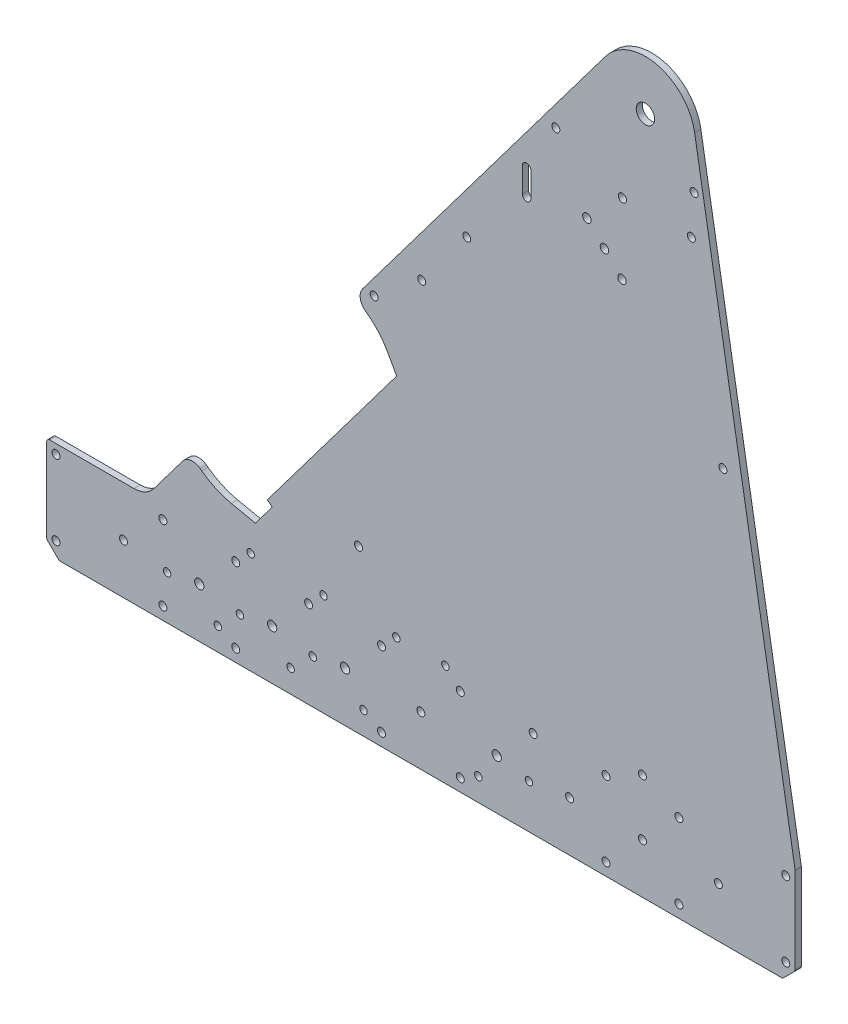
SolidWorks part; units mm, degrees
ref_plane "Front Plane" through (0, 0, 0) normal (0, 0, 1) x (1, 0, 0)
ref_plane "Top Plane" through (0, 0, 0) normal (0, 1, 0) x (1, 0, 0)
ref_plane "Right Plane" through (0, 0, 0) normal (1, 0, 0) x (0, 0, -1)
sketch "Sketch1" plane through (0, 0, 0) normal (0, 0, 1) x (1, 0, 0)
  line L1 (0, 0) -> (381, 0)
  line L2 (0, 0) -> (0, 50.8)
  line L4 (381, 0) -> (381, 50.8)
  line L5 (381, 50.8) -> (329.8374, 350.3513)
  line L6 (0, 50.8) -> (44.463, 50.8)
  line L7 (54.6105, 55.8634) -> (73.025, 80.3327)
  line L9 (112.3265, 79.755) -> (178.1676, 167.245)
  line L11 (157.0275, 191.9556) -> (284.5049, 361.3482)
  line L12 (112.3265, 79.755) -> (114.8634, 77.8458)
  line L13 (114.8634, 77.8458) -> (106.2722, 66.4299)
  line L14 (157.0275, 191.9556) -> (169.7119, 182.4098)
  line L15 (169.7119, 182.4098) -> (178.1676, 167.245)
  line L16 (73.025, 80.3327) -> (85.7094, 70.7869)
  line L17 (85.7094, 70.7869) -> (106.2722, 66.4299)
  line L18 (169.7119, 182.4098) -> (85.7094, 70.7869) construction
  arc A0 (284.5049, 361.3482) -> (329.8374, 350.3513) centre (304.8, 346.075) cw
  arc A1 (44.463, 50.8) -> (54.6105, 55.8634) centre (44.463, 63.5) ccw
  point P11 (50.8, 50.8)
  dimension "D4" = 346.075
  dimension "D7" = 12.7
  dimension "D5" = 25.4
  dimension "D1" = 50.8
  dimension "D2" = 381
  dimension "D3" = 76.2
  dimension "D6" = 50.8
  dimension "D8" = 123.825
  dimension "D9" = 139.7
  dimension "D10" = 15.875
  dimension "D11" = 31.75
  dimension "D12" = 73.025
  dimension "D13" = 3.175
  dimension "D14" = 14.2875
  dimension "D15" = 115
extrude "Boss-Extrude1" add sketch "Sketch1" along normal blind 3.175
sketch "Sketch2" plane through (0, 0, 3.175) normal (0, 0, 1) x (1, 0, 0)
  line L1 (190.5, 50.8) -> (190.5, 0) construction
  line L3 (0, 0) -> (381, 0) construction
  line L5 (0, 6.35) -> (0, 0)
  line L6 (0, 50.8) -> (0, 0) construction
  line L7 (0, 0) -> (6.35, 0)
  line L8 (6.35, 0) -> (0, 6.35)
  line L9 (381, 0) -> (374.65, 0)
  line L10 (374.65, 0) -> (381, 6.35)
  line L11 (381, 6.35) -> (381, 0)
  circle A19 centre (4.7625, 46.0375) radius 2.032
  circle A20 centre (4.7625, 7.9375) radius 2.032
  circle A21 centre (376.2375, 7.9375) radius 2.032
  circle A22 centre (376.2375, 46.0375) radius 2.032
  dimension "D21" = 6.35
  dimension "D27" = 4.064
  dimension "D4" = 46.0375
  dimension "D22" = 6.35
  dimension "D25" = 4.7625
  dimension "D28" = 7.9375
extrude "Cut-Extrude1" cut sketch "Sketch2" against normal up to next
sketch "Sketch5" plane through (0, 0, 3.175) normal (0, 0, 1) x (1, 0, 0)
  line L0 (151.892, 25.4) -> (229.108, 25.4) construction
  line L1 (229.108, 25.4) -> (341.884, 25.4) construction
  circle A0 centre (39.116, 25.4) radius 2.032
  circle A1 centre (59.182, 6.35) radius 2.032
  circle A2 centre (59.182, 44.45) radius 2.032
  circle A3 centre (96.266, 44.45) radius 2.032
  circle A4 centre (133.35, 44.45) radius 2.032
  circle A5 centre (170.434, 44.45) radius 2.032
  circle A6 centre (210.566, 44.45) radius 2.032
  circle A7 centre (210.566, 6.35) radius 2.032
  circle A8 centre (170.434, 6.35) radius 2.032
  circle A9 centre (247.65, 44.45) radius 2.032
  circle A10 centre (266.192, 25.4) radius 2.032
  circle A11 centre (39.116, 25.4) radius 2.286 construction
  circle A12 centre (59.182, 44.45) radius 1.905 construction
  circle A13 centre (59.182, 6.35) radius 1.905 construction
  circle A14 centre (96.266, 44.45) radius 1.905 construction
  circle A15 centre (133.35, 44.45) radius 1.905 construction
  circle A16 centre (170.434, 44.45) radius 1.905 construction
  circle A17 centre (170.434, 6.35) radius 2.159 construction
  circle A18 centre (210.566, 6.35) radius 2.159 construction
  circle A19 centre (210.566, 44.45) radius 1.905 construction
  circle A20 centre (247.65, 44.45) radius 1.905 construction
  circle A21 centre (266.192, 25.4) radius 2.286 construction
  circle A22 centre (77.724, 25.4) radius 2.3813
  circle A23 centre (114.808, 25.4) radius 2.3813
  circle A24 centre (151.892, 25.4) radius 2.3813
  circle A25 centre (229.108, 25.4) radius 2.3813
  circle A26 centre (190.5, 25.4) radius 2.032
  circle A28 centre (303.276, 25.4) radius 2.032
  circle A29 centre (341.884, 25.4) radius 2.032
  circle A30 centre (77.724, 25.4) radius 7.366 construction
  circle A31 centre (114.808, 25.4) radius 7.366 construction
  circle A32 centre (151.892, 25.4) radius 7.366 construction
  circle A33 centre (229.108, 25.4) radius 7.366 construction
  dimension "D1" = 4.064
  dimension "D2" = 4.7625
  dimension "D3" = 37.084
  dimension "D4" = 38.608
  dimension "D5" = 38.608
extrude "Cut-Extrude4" cut sketch "Sketch5" against normal through all
sketch "Sketch6" plane through (0, 0, 3.175) normal (0, 0, 1) x (1, 0, 0)
  line L0 (6.35, 0) -> (374.65, 0) construction
  line L1 (266.192, 25.4) -> (303.276, 25.4) construction
  line L2 (284.734, 6.35) -> (284.734, 44.45) construction
  line L3 (151.892, 25.4) -> (114.808, 25.4) construction
  line L4 (114.808, 25.4) -> (77.724, 25.4) construction
  circle A0 centre (284.734, 44.45) radius 2.032
  circle A1 centre (284.734, 6.35) radius 2.032
  circle A2 centre (321.818, 6.35) radius 2.032
  circle A3 centre (321.818, 44.45) radius 2.032
  circle A4 centre (96.266, 6.35) radius 2.032
  circle A6 centre (303.276, 53.975) radius 2.032
  arc A7 (304.329, 52.3875) -> (302.223, 52.3875) centre (303.276, 53.975) ccw construction
  point P8 (284.734, 25.4)
  point P9 (284.734, 25.4)
  point P28 (96.266, 25.4)
  dimension "D1" = 4.064
  dimension "D2" = 6.35
  dimension "D3" = 37.084
extrude "Cut-Extrude5" cut sketch "Sketch6" against normal through all
sketch "Sketch3" plane through (0, 0, 3.175) normal (0, 0, 1) x (1, 0, 0)
  line L0 (73.025, 80.3327) -> (54.6105, 55.8634) construction
  line L1 (381, 6.35) -> (381, 50.8) construction
  line L2 (6.35, 0) -> (374.65, 0) construction
  line L3 (304.8, 346.075) -> (293.0652, 303.202) construction
  line L4 (275.0085, 285.3381) -> (293.0652, 303.202) construction
  line L5 (275.0085, 285.3381) -> (283.9404, 276.3098) construction
  line L6 (283.9404, 276.3098) -> (292.8724, 267.2815) construction
  line L7 (381, 50.8) -> (329.8374, 350.3513) construction
  line L8 (244.3127, 279.4) -> (244.3127, 292.1) construction
  line L9 (0, 50.8) -> (0, 6.35) construction
  line L12 (284.5049, 361.3482) -> (157.0275, 191.9556) construction
  line L13 (242.1537, 279.4) -> (242.1537, 292.1)
  line L14 (246.4717, 279.4) -> (246.4717, 292.1)
  line L15 (190.9415, 215.9) -> (213.8513, 246.3426) construction
  circle A0 centre (304.8, 346.075) radius 4.699
  circle A1 centre (166.6875, 196.85) radius 2.032
  circle A2 centre (158.75, 82.55) radius 2.032
  circle A3 centre (293.0652, 303.202) radius 2.0955
  circle A5 centre (275.0085, 285.3381) radius 2.159
  circle A6 centre (283.9404, 276.3098) radius 2.159
  circle A7 centre (292.8724, 267.2815) radius 2.159
  circle A8 centre (328.1868, 303.4404) radius 2.032
  circle A9 centre (344.223, 209.55) radius 2.032
  circle A12 centre (259.2118, 317.1783) radius 2.032
  arc A26 (242.1537, 279.4) -> (246.4717, 279.4) centre (244.3127, 279.4) ccw
  arc A27 (246.4717, 292.1) -> (242.1537, 292.1) centre (244.3127, 292.1) ccw
  circle A28 centre (213.8513, 246.3426) radius 2.032
  circle A29 centre (190.9415, 215.9) radius 2.032
  circle A30 centre (329.5323, 323.85) radius 2.032
  point P27 (244.3127, 285.75)
  dimension "D1" = 9.398
  dimension "D3" = 4.064
  dimension "D6" = 4.064
  dimension "D11" = 4.318
  dimension "D10" = 4.191
  dimension "D13" = 4.064
  dimension "D20" = 4.064
  dimension "D18" = 2.159
  dimension "D28" = 12.7
  dimension "D34" = 4.7625
  dimension "D21" = 38.1
  dimension "D19" = 9.525
  dimension "D29" = 4.064
  dimension "D33" = 4.064
  dimension "D4" = 222.25
  dimension "D5" = 82.55
  dimension "D7" = 25.4
  dimension "D8" = 12.7
  dimension "D9" = 44.45
  dimension "D12" = 12.7
  dimension "D14" = 9.525
  dimension "D15" = 9.525
  dimension "D16" = 95.25
  dimension "D17" = 209.55
  dimension "D22" = 12.7
  dimension "D23" = 53.975
  dimension "D24" = 6.35
  dimension "D25" = 196.85
  dimension "D26" = 166.6875
  dimension "D27" = 279.4
  dimension "D30" = 25
  dimension "D31" = 150
  dimension "D32" = 215.9
  dimension "D35" = 22.225
extrude "Cut-Extrude2" cut sketch "Sketch3" against normal through all
fillet "Fillet1" radius 1.5875 6 edges at (374.65, 0, 1.5875) (381, 6.35, 1.5875) (381, 50.8, 1.5875) (6.35, 0, 1.5875) (0, 6.35, 1.5875) (0, 50.8, 1.5875)
sketch "Sketch4" plane through (0, 0, 0) normal (0, 0, -1) x (-1, 0, 0)
  circle A0 centre (-61.3181, 22.2981) radius 1.905 construction
  circle A1 centre (-87.1313, 11.606) radius 1.905 construction
  circle A2 centre (-98.4021, 22.2981) radius 1.905 construction
  circle A3 centre (-124.2153, 11.606) radius 1.905 construction
  circle A4 centre (-135.4861, 22.2981) radius 1.905 construction
  circle A5 centre (-161.2993, 11.606) radius 1.905 construction
  circle A6 centre (-245.5139, 22.2981) radius 1.905 construction
  circle A7 centre (-219.7007, 11.606) radius 1.905 construction
  circle A8 centre (-202.982, 51.9684) radius 1.905 construction
  circle A9 centre (-178.018, 51.9684) radius 1.905 construction
  circle A10 centre (-140.934, 51.9684) radius 1.905 construction
  circle A11 centre (-103.85, 51.9684) radius 1.905 construction
  circle A12 centre (-61.3181, 22.2981) radius 1.905
  circle A13 centre (-87.1313, 11.606) radius 1.905
  circle A14 centre (-98.4021, 22.2981) radius 1.905
  circle A15 centre (-124.2153, 11.606) radius 1.905
  circle A16 centre (-135.4861, 22.2981) radius 1.905
  circle A17 centre (-161.2993, 11.606) radius 1.905
  circle A18 centre (-245.5139, 22.2981) radius 1.905
  circle A19 centre (-219.7007, 11.606) radius 1.905
  circle A20 centre (-202.982, 51.9684) radius 1.905
  circle A21 centre (-178.018, 51.9684) radius 1.905
  circle A22 centre (-140.934, 51.9684) radius 1.905
  circle A23 centre (-103.85, 51.9684) radius 1.905
extrude "Cut-Extrude3" cut sketch "Sketch4" against normal up to next
fillet "Fillet2" radius 38.1 2 edges at (85.7094, 70.7869, 1.5875) (169.7119, 182.4098, 1.5875)
fillet "Fillet3" radius 6.35 2 edges at (73.025, 80.3327, 1.5875) (157.0275, 191.9556, 1.5875)
